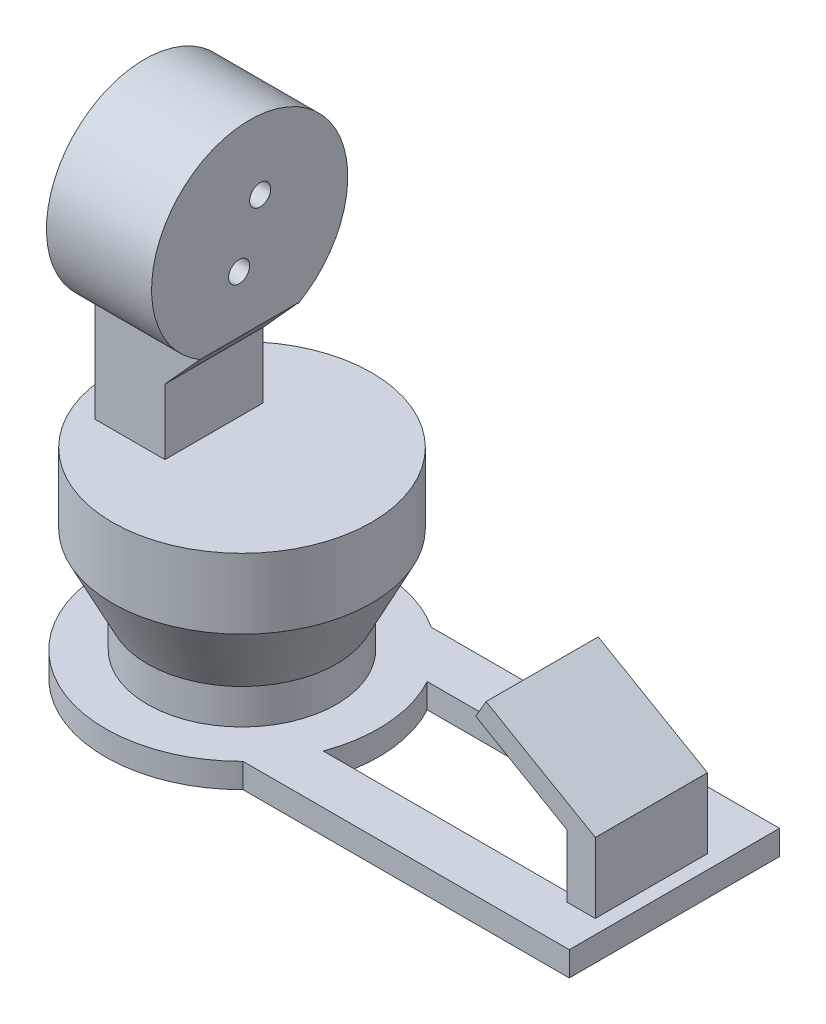
SolidWorks part; units mm, degrees
ref_plane "Alzado" through (0, 0, 0) normal (0, 0, 1) x (1, 0, 0)
ref_plane "Planta" through (0, 0, 0) normal (0, 1, 0) x (1, 0, 0)
ref_plane "Vista lateral" through (0, 0, 0) normal (1, 0, 0) x (0, 0, -1)
sketch "Croquis1" plane through (0, 0, 0) normal (0, 1, 0) x (1, 0, 0)
  line L0 (60.4126, -13.7116) -> (-13.8651, -13.7116)
  line L1 (60.4126, -13.7116) -> (60.4126, 16.2884)
  line L3 (60.4126, 16.2884) -> (-10.721, 16.2884)
  line L7 (-17.1457, 9.2884) -> (53.4126, 9.2884)
  line L9 (-18.3086, -6.7116) -> (53.4126, -6.7116)
  line L10 (53.4126, 9.2884) -> (53.4126, -6.7116)
  circle A0 centre (0, 0) radius 19.5
  point P4 (30, 1.2884)
  point P5 (30, 1.2884)
  dimension "D1" = 39
  dimension "D2" = 30
  dimension "D3" = 7
  dimension "D4" = 7
  dimension "D5" = 7
extrude "Saliente-Extruir1" add sketch "Croquis1" along normal blind 3.5 contours A0 L0 L1 L3 L7 L10 L9 | L9 A0 L7 | L7 A0 L3 | L0 A0 L9 | L0 A0 | L3 A0 region at (37.1389, 0, 13.1312) region at (0, 0, 16.0592) region at (0, 0, 10.056) region at (0, 0, -1.2094) region at (0, 0, -12.5352) region at (0, 0, -17.5825)
sketch "Croquis2" plane through (0, 3.5, 0) normal (0, 1, 0) x (1, 0, 0)
  circle A0 centre (0, 0) radius 13.5
  dimension "D1" = 27
extrude "Saliente-Extruir2" add sketch "Croquis2" along normal blind 5
ref_plane "Plano1" through (0, 18.5, 0) normal (0, 1, 0) x (1, 0, 0)
sketch "Croquis4" plane through (0, 18.5, 0) normal (0, 1, 0) x (1, 0, 0)
  circle A0 centre (0, 0) radius 18.5
  dimension "D1" = 37
sketch "Croquis5" plane through (0, 8.5, 0) normal (0, 1, 0) x (1, 0, 0)
  circle A0 centre (0, 0) radius 13.5
loft "Recubrir2" add profiles "Croquis4", "Croquis5" connector at (-17.1621, 18.5, 6.9075) connector at (-12.0896, 8.5, 6.0076)
sketch "Croquis6" plane through (0, 18.5, 0) normal (0, 1, 0) x (1, 0, 0)
  circle A0 centre (0, 0) radius 18.5
extrude "Saliente-Extruir3" add sketch "Croquis6" along normal blind 10
sketch "Croquis7" plane through (0, 28.5, 0) normal (0, 1, 0) x (1, 0, 0)
  line L1 (-13.9959, 7) -> (-3.9959, 7)
  line L2 (-13.9959, 7) -> (-13.9959, -7)
  line L3 (-13.9959, -7) -> (-3.9959, -7)
  line L4 (-3.9959, 7) -> (-3.9959, -7)
  point P4 (-3.9959, 0)
  dimension "D1" = 14
  dimension "D2" = 10
extrude "Saliente-Extruir4" add sketch "Croquis7" along normal blind 9.335
sketch "Croquis8" plane through (0, 0, 0) normal (0, 0, 1) x (1, 0, 0)
  line L0 (-13.9959, 37.835) -> (-13.9959, 43.365)
  line L1 (-13.9959, 43.365) -> (1.0041, 43.365)
  line L2 (1.0041, 43.365) -> (-3.9959, 37.835)
  line L3 (-3.9959, 37.835) -> (-13.9959, 37.835)
  dimension "D1" = 5
  dimension "D2" = 5.53
extrude "Saliente-Extruir5" add sketch "Croquis8" along normal mid plane 14
sketch "Croquis9" plane through (-13.9959, 0, 0) normal (-1, 0, 0) x (0, 0, 1)
  line L2 (-7, 43.365) -> (-7, 28.5) construction
  line L3 (-7, 43.365) -> (-7, 28.5)
  circle A0 centre (-0.0917, 55.434) radius 14
  line M3 (7, 28.5) -> (7, 43.365)
  line M4 (7, 43.365) -> (-7, 43.365)
  line M5 (-7, 43.365) -> (-7, 28.5)
  dimension "D1" = 28
extrude "Saliente-Extruir6" add sketch "Croquis9" against normal blind 15 contours A0 M3 M5 M4 region at (-13.9959, 55.8325, -0.0918)
sketch "Croquis10" plane through (0, 0, 0) normal (0, 0, 1) x (1, 0, 0)
  line L0 (60.4126, 3.5) -> (13.8651, 3.5) construction
  line L1 (58.4126, 3.5) -> (54.4126, 3.5)
  line L2 (58.4126, 3.5) -> (58.4126, 13.5)
  line L4 (54.4126, 3.5) -> (54.4126, 12.42)
  line L5 (60.4126, 3.5) -> (60.4126, 0) construction
  line L6 (58.4126, 13.5) -> (58.4203, 13.5133)
  line L7 (58.4203, 13.5133) -> (42.8318, 22.5133)
  line L8 (42.8318, 22.5133) -> (41.3565, 19.9579)
  line L9 (41.3565, 19.9579) -> (54.4126, 12.42)
  dimension "D1" = 2
  dimension "D4" = 8.92
  dimension "D5" = 150
  dimension "D6" = 18
extrude "Saliente-Extruir7" add sketch "Croquis10" along normal mid plane 16
sketch "Croquis11" plane through (-13.9959, 0, 0) normal (-1, 0, 0) x (0, 0, 1)
  line L0 (-0.0917, 55.434) -> (13.9083, 55.434)
  circle A0 centre (-1.5917, 59.434) radius 1.5
  circle A1 centre (1.4083, 51.434) radius 1.5
  arc A2 (7, 43.3631) -> (-7, 43.2572) centre (-0.0917, 55.434) ccw construction
  dimension "D3" = 3
  dimension "D4" = 3
  dimension "D1" = 8
  dimension "D2" = 4
extrude "Cortar-Extruir1" cut sketch "Croquis11" against normal through all contours A0 | A1 region at (-13.9959, 59.434, -1.5917) region at (-13.9959, 51.434, 1.4083)
